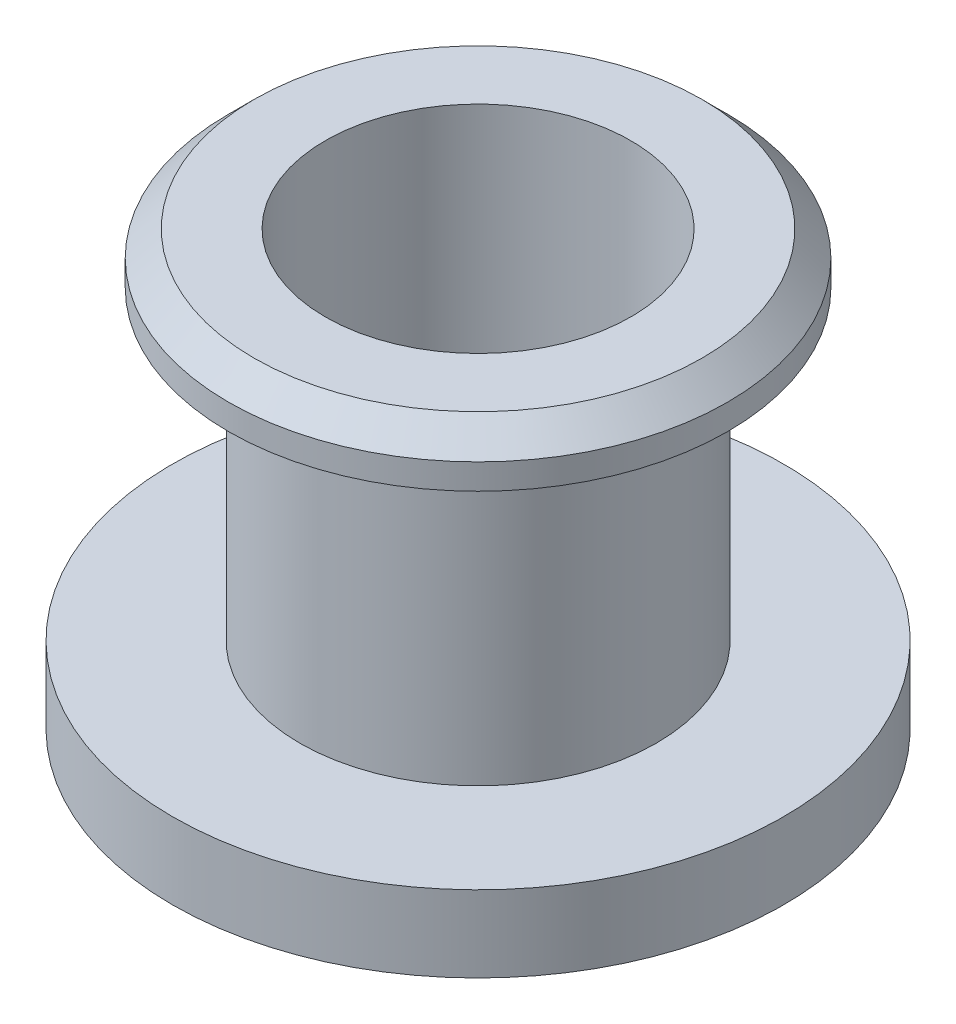
SolidWorks part; units mm, degrees
material "PC High Viscosity"
ref_plane "Front Plane" through (0, 0, 0) normal (0, 0, 1) x (1, 0, 0)
ref_plane "Top Plane" through (0, 0, 0) normal (0, 1, 0) x (1, 0, 0)
ref_plane "Right Plane" through (0, 0, 0) normal (1, 0, 0) x (0, 0, -1)
ref_axis "CentralAxis" through (0, -1.93, 0) along (0, 1, 0)
sketch "HeadS" plane through (0, 0, 0) normal (0, 1, 0) x (1, 0, 0)
  circle A0 centre (0, 0) radius 6
  dimension "Dia" = 12
extrude "Head" add sketch "HeadS" against normal blind 1.5
sketch "TubeEncapsulationBodyS" plane through (0, 0, 0) normal (0, -1, 0) x (-1, 0, 0)
  circle A0 centre (0, 0) radius 3.5
  dimension "Dia" = 7
extrude "TubeEncapsulationBody" add sketch "TubeEncapsulationBodyS" against normal blind 6
sketch "TubeAccessS" plane through (0, -1.5, 0) normal (0, 1, 0) x (1, 0, 0)
  circle A0 centre (0, 0) radius 3
  circle A1 centre (0, 0) radius 3.5 construction
  dimension "D1" = 0.5
  dimension "D2" = 6
extrude "TubeAccess" cut sketch "TubeAccessS" along normal through all
sketch "LockingBodyS" plane through (0, 6, 0) normal (0, 1, 0) x (1, 0, 0)
  circle A0 centre (0, 0) radius 3 construction
  circle A1 centre (0, 0) radius 3
  circle A2 centre (0, 0) radius 4.9
  dimension "DiaControl" = 1.9
extrude "LockingBody" add sketch "LockingBodyS" along normal blind 1
chamfer "OpenClampC" distance 0.5 angle 45 1 edges at (0, 7, 4.9)
